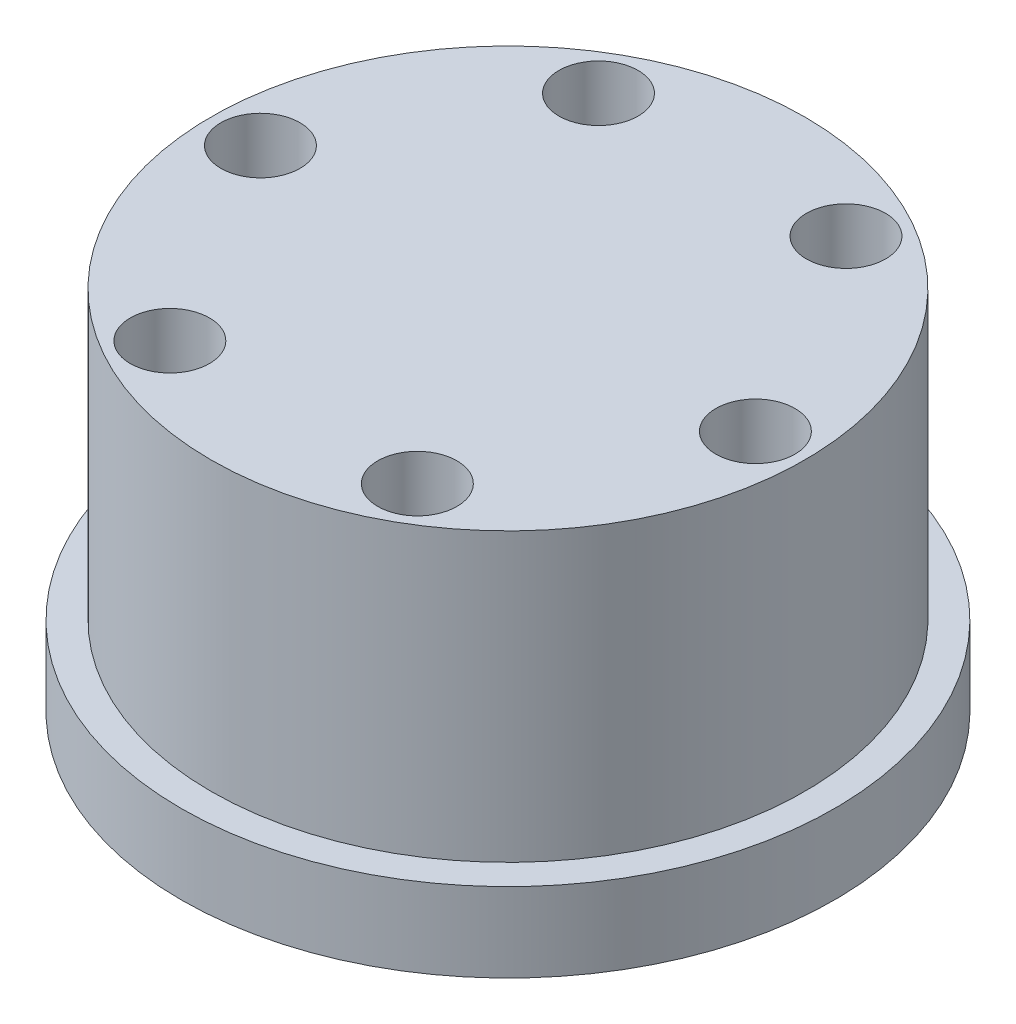
SolidWorks part; units mm, degrees
ref_plane "Front Plane" through (0, 0, 0) normal (0, 0, 1) x (1, 0, 0)
ref_plane "Top Plane" through (0, 0, 0) normal (0, 1, 0) x (1, 0, 0)
ref_plane "Right Plane" through (0, 0, 0) normal (1, 0, 0) x (0, 0, -1)
sketch "Sketch1" plane through (0, 0, 0) normal (0, 1, 0) x (1, 0, 0)
  circle A0 centre (0, 0) radius 16.5
  circle A1 centre (0, 0) radius 12.5 construction
  circle A2 centre (0, 12.5) radius 1.5
  circle A3 centre (10.8253, 6.25) radius 1.5
  circle A4 centre (10.8253, -6.25) radius 1.5
  circle A5 centre (0, -12.5) radius 1.5
  circle A6 centre (-10.8253, -6.25) radius 1.5
  circle A7 centre (-10.8253, 6.25) radius 1.5
  point P19 (0, 0)
  dimension "D1" = 33
  dimension "D2" = 25
  dimension "D3" = 3
  dimension "D4" = 6
extrude "Boss-Extrude1" add sketch "Sketch1" along normal blind 4
sketch "Sketch2" plane through (0, 4, 0) normal (0, 1, 0) x (1, 0, 0)
  circle A0 centre (0, 0) radius 15
  dimension "D1" = 30
extrude "Boss-Extrude2" add sketch "Sketch2" along normal blind 14.5
sketch "Sketch3" plane through (0, 0, 0) normal (0, -1, 0) x (1, 0, 0)
  circle A0 centre (0, 0) radius 9
  dimension "D1" = 18
extrude "Cut-Extrude1" cut sketch "Sketch3" against normal blind 2
sketch "Sketch4" plane through (0, 2, 0) normal (0, -1, 0) x (1, 0, 0)
  circle A0 centre (0, 0) radius 6.6
  dimension "D1" = 13.2
extrude "Cut-Extrude2" cut sketch "Sketch4" against normal blind 4
sketch "Sketch5" plane through (0, 18.5, 0) normal (0, 1, 0) x (1, 0, 0)
  circle A0 centre (0, 0) radius 12.5 construction
  circle A1 centre (-12.5, 0) radius 2
  circle A2 centre (-6.25, 10.8253) radius 2
  circle A3 centre (6.25, 10.8253) radius 2
  circle A4 centre (12.5, 0) radius 2
  circle A5 centre (6.25, -10.8253) radius 2
  circle A6 centre (-6.25, -10.8253) radius 2
  point P17 (0, 0)
  dimension "D1" = 25
  dimension "D2" = 4
  dimension "D3" = 6
extrude "Cut-Extrude3" cut sketch "Sketch5" against normal blind 6.5
